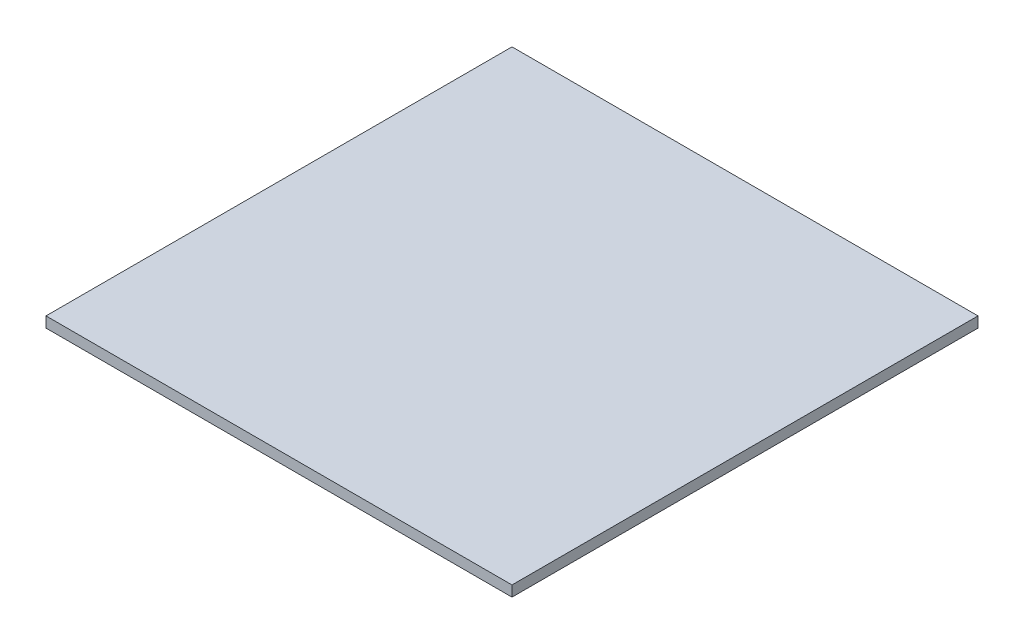
SolidWorks part; units mm, degrees
ref_plane "Front Plane" through (0, 0, 0) normal (0, 0, 1) x (1, 0, 0)
ref_plane "Top Plane" through (0, 0, 0) normal (0, 1, 0) x (1, 0, 0)
ref_plane "Right Plane" through (0, 0, 0) normal (1, 0, 0) x (0, 0, -1)
sketch "Sketch1" plane through (0, 0, 0) normal (0, 1, 0) x (1, 0, 0)
  line L0 (-539.4098, 0) -> (19.3902, 0)
  line L1 (19.3902, 0) -> (19.3902, 558.8)
  line L2 (19.3902, 558.8) -> (-539.4098, 558.8)
  line L3 (-539.4098, 558.8) -> (-539.4098, 0)
extrude "Boss-Extrude1" add sketch "Sketch1" along normal blind 12.7
